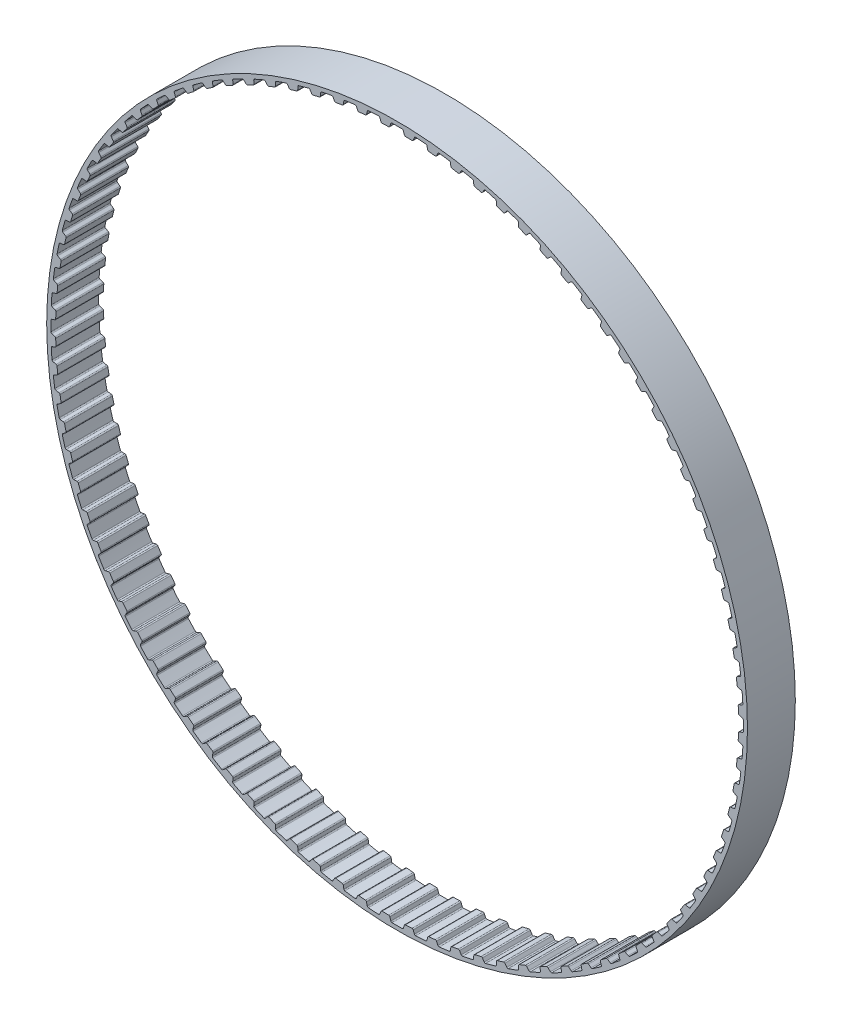
SolidWorks part; units mm, degrees
ref_plane "Front Plane" through (0, 0, 0) normal (0, 0, 1) x (1, 0, 0)
ref_plane "Top Plane" through (0, 0, 0) normal (0, 1, 0) x (1, 0, 0)
ref_plane "Right Plane" through (0, 0, 0) normal (1, 0, 0) x (0, 0, -1)
sketch "Sketch1" plane through (0, 0, 0) normal (0, 0, 1) x (1, 0, 0)
  line L0 (0, 0) -> (-4.6402, 135.8324) construction
  line L1 (0, 0) -> (4.6402, 135.8324) construction
  line L2 (4.6402, 135.8324) -> (-4.6402, 135.8324) construction
  line L3 (4.6402, 135.8324) -> (-4.6402, 135.8324) construction
  circle A0 centre (0, 0) radius 139.4676
  circle A1 centre (0, 0) radius 135.9116
  circle A2 centre (0, 0) radius 137.8166 construction
  dimension "OD" = 278.9352
  dimension "Angle Distance" = 3.913
  dimension "hs" = 3.556
  dimension "ht" = 1.905
extrude "Boss-Extrude1" add sketch "Sketch1" along normal mid plane 19.05
sketch "Sketch2" plane through (0, 0, 0) normal (0, 0, 1) x (1, 0, 0)
  line L1 (0, 139.4676) -> (0, 0) construction
  line L2 (-4.7625, 136.8422) -> (4.7625, 136.8422) construction
  line L4 (-3.0019, 135.8883) -> (-6.2785, 135.7764)
  line L5 (-3.0019, 135.8883) -> (-2.3804, 137.796)
  line L6 (-6.2785, 135.7764) -> (-7.0286, 137.6372)
  line L7 (0, 0) -> (-4.6402, 135.8324) construction
  line L8 (-2.3804, 137.796) -> (-7.0286, 137.6372) construction
  line L9 (2.3804, 137.796) -> (7.0286, 137.6372) construction
  line L10 (6.2785, 135.7764) -> (7.0286, 137.6372)
  line L11 (3.0019, 135.8883) -> (2.3804, 137.796)
  line L12 (3.0019, 135.8883) -> (6.2785, 135.7764)
  line L13 (0, 0) -> (53.3719, 128.8513) construction
  line L14 (-4.7625, 136.8422) -> (-14.2645, 136.18) construction
  line L15 (-9.5135, 136.5111) -> (0, 0) construction
  line L16 (-14.2645, 136.18) -> (-14.1589, 135.1721) construction
  circle A0 centre (0, 0) radius 137.8166 construction
  circle A1 centre (0, 0) radius 137.8166
  circle A2 centre (0, 0) radius 136.8422 construction
  circle A4 centre (0, 0) radius 139.4676 construction
  circle A5 centre (0, 0) radius 135.9116 construction
  point P16 (-2.6912, 136.8422)
  point P20 (0, 136.8422)
  dimension "D1" = 22.5
  dimension "bt" = 4.6482
  dimension "b" = 40
  dimension "Pitch" = 9.525
sketch "Sketch3" plane through (0, 0, 0) normal (0, 0, 1) x (1, 0, 0)
  line L0 (-3.3641, 135.87) -> (3.3641, 135.87)
  line L2 (-3.0019, 135.8883) -> (-2.3804, 137.796) construction
  line L3 (3.0019, 135.8883) -> (2.3804, 137.796) construction
  line L5 (-2.8937, 136.2204) -> (-2.4928, 137.4512)
  line L7 (2.8937, 136.2204) -> (2.4928, 137.4512)
  arc A0 (2.8937, 136.2204) -> (3.3641, 135.87) centre (3.3767, 136.3778) ccw
  circle A1 centre (0, 0) radius 137.8166 construction
  arc A2 (2.0172, 137.8018) -> (-2.0172, 137.8018) centre (0, 0) ccw
  arc A3 (-2.8937, 136.2204) -> (-3.3641, 135.87) centre (-3.3767, 136.3778) cw
  arc A4 (2.4928, 137.4512) -> (2.0172, 137.8018) centre (2.0097, 137.2939) ccw
  arc A5 (-2.4928, 137.4512) -> (-2.0172, 137.8018) centre (-2.0097, 137.2939) cw
  circle A6 centre (0, 0) radius 135.9116 construction
  arc A7 (-3.3641, 135.87) -> (3.3641, 135.87) centre (0, 0) ccw construction
  dimension "ra" = 0.508
  dimension "rr" = 0.508
extrude "Cut-Extrude1" cut sketch "Sketch3" against normal mid plane 19.05
pattern_circular "CirPattern1" count 92 over 360 about axis through (0, 0, 9.525) along (0, 0, -1) of "Cut-Extrude1"
equation "\"D1@Cut-Extrude1\" = \"Width@Boss-Extrude1\""
